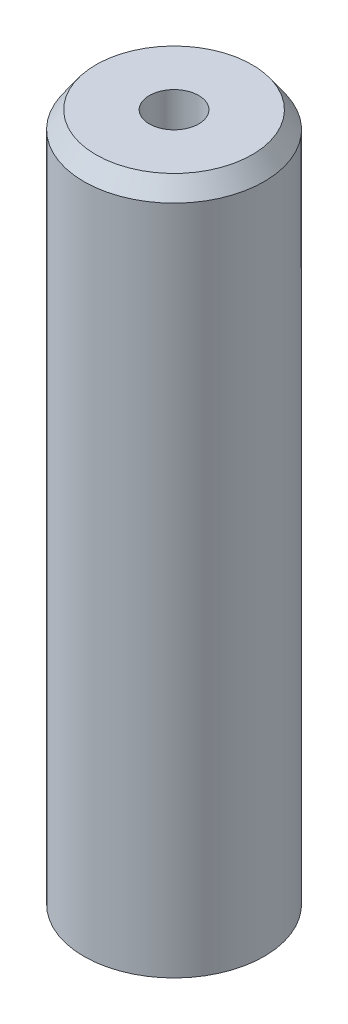
SolidWorks part; units mm, degrees
ref_plane "Front Plane" through (0, 0, 0) normal (0, 0, 1) x (1, 0, 0)
ref_plane "Top Plane" through (0, 0, 0) normal (0, 1, 0) x (1, 0, 0)
ref_plane "Right Plane" through (0, 0, 0) normal (1, 0, 0) x (0, 0, -1)
sketch "Sketch1" plane through (0, 0, 0) normal (0, 1, 0) x (1, 0, 0)
  circle A0 centre (0, 0) radius 5
  dimension "SHAFT_OD" = 10
extrude "Boss-Extrude1" add sketch "Sketch1" along normal blind 38.8417
sketch "Sketch2" plane through (0, 0, 0) normal (0, 1, 0) x (1, 0, 0)
  circle A0 centre (0, 0) radius 1.3694
  dimension "BORE_D" = 2.7388
extrude "Cut-Extrude1" cut sketch "Sketch2" along normal through all
chamfer "Chamfer1" distance 0.9538 angle 35.097 2 edges at (0, 38.8417, 5) (0, 0, 5) first distance on face at (0, 38.8417, 5) first distance on face at (0, 0, 1.3694)
